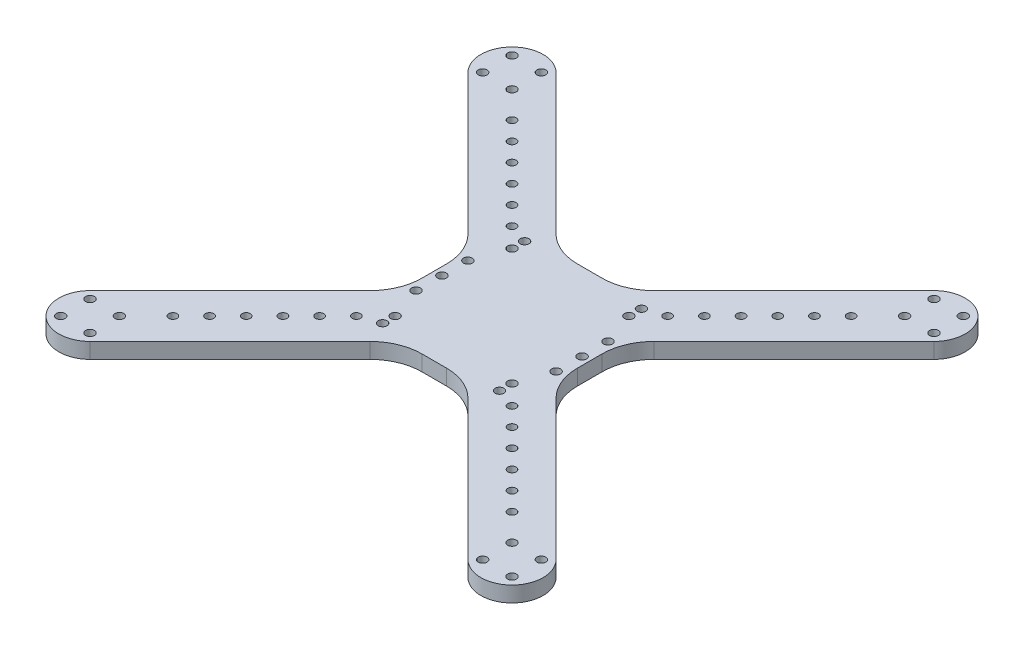
SolidWorks part; units mm, degrees
material "Carbon Fiber"
ref_plane "Front Plane" through (0, 0, 0) normal (0, 0, 1) x (1, 0, 0)
ref_plane "Top Plane" through (0, 0, 0) normal (0, 1, 0) x (1, 0, 0)
ref_plane "Right Plane" through (0, 0, 0) normal (1, 0, 0) x (0, 0, -1)
sketch "Sketch1" plane through (0, 0, 0) normal (0, 1, 0) x (1, 0, 0)
  line L0 (-81.3173, 81.3173) -> (81.3173, -81.3173) construction
  line L1 (-98.425, -98.425) -> (98.425, -98.425) construction
  line L2 (-98.425, -98.425) -> (-98.425, 98.425) construction
  line L3 (-98.425, 98.425) -> (98.425, 98.425) construction
  line L4 (98.425, -98.425) -> (98.425, 98.425) construction
  line L5 (-98.425, -98.425) -> (98.425, 98.425) construction
  line L6 (-98.425, 98.425) -> (98.425, -98.425) construction
  line L7 (-72.832, 89.8026) -> (-13.0294, 30)
  line L8 (-89.8026, 72.832) -> (-30, 13.0294)
  line L9 (0, 98.425) -> (0, -98.425) construction
  line L10 (81.3173, 81.3173) -> (-81.3173, -81.3173) construction
  line L11 (72.832, 89.8026) -> (13.0294, 30)
  line L12 (89.8026, 72.832) -> (30, 13.0294)
  line L13 (-30, -13.0294) -> (-89.8026, -72.832)
  line L14 (-13.0294, -30) -> (13.0294, -30)
  line L15 (-30, -13.0294) -> (-30, 13.0294)
  line L16 (-13.0294, 30) -> (13.0294, 30)
  line L17 (30, -13.0294) -> (30, 13.0294)
  line L18 (-30, -30) -> (30, 30) construction
  line L19 (-30, 30) -> (30, -30) construction
  line L20 (-13.0294, -30) -> (-72.832, -89.8026)
  line L21 (30, -13.0294) -> (89.8026, -72.832)
  line L22 (13.0294, -30) -> (72.832, -89.8026)
  arc A0 (-72.832, 89.8026) -> (-89.8026, 72.832) centre (-81.3173, 81.3173) ccw
  arc A1 (72.832, -89.8026) -> (89.8026, -72.832) centre (81.3173, -81.3173) ccw
  circle A2 centre (-81.3173, 81.3173) radius 8 construction
  circle A3 centre (81.3173, -81.3173) radius 8 construction
  circle A4 centre (-81.3173, -81.3173) radius 8 construction
  circle A5 centre (81.3173, 81.3173) radius 8 construction
  arc A6 (72.832, 89.8026) -> (89.8026, 72.832) centre (81.3173, 81.3173) cw
  arc A7 (-72.832, -89.8026) -> (-89.8026, -72.832) centre (-81.3173, -81.3173) cw
  point P0 (0, 0)
  point P8 (0, 0)
  point P23 (0, 0)
  point P29 (0, 0)
  point P42 (30, 0)
  dimension "D2" = 12
  dimension "D4" = 16
  dimension "D6" = 12
  dimension "D9" = 12
  dimension "D10" = 12
  dimension "D1" = 196.85
  dimension "D3" = 115
  dimension "D5" = 115
  dimension "D8" = 26.0589
  dimension "D11" = 30
  dimension "D12" = 30
extrude "Boss-Extrude1" add sketch "Sketch1" along normal blind 6
fillet "Fillet1" radius 20 8 edges at (-30, 3, -13.0294) (-30, 3, 13.0294) (-13.0294, 3, -30) (13.0294, 3, -30) (30, 3, 13.0294) (30, 3, -13.0294) (13.0294, 3, 30) (-13.0294, 3, 30)
ref_axis "Axis1" through (0, 6.3, 0) along (0, -1, 0)
ref_plane "Plane1" through (0, 0, 0) normal (-0.7071, 0, 0.7071) x (0, -1, 0)
sketch "Sketch2" plane through (0, 6, 0) normal (0, 1, 0) x (1, 0, 0)
  line L0 (0, 0) -> (-25, 0)
  line L1 (-25, 0) -> (-25, -25)
  line L2 (-25, -25) -> (0, -25)
  line L3 (0, -25) -> (0, 0)
  circle A1 centre (-22.525, -22.525) radius 1.7
  dimension "D4" = 3.4
  dimension "D1" = 25
  dimension "D2" = 22.525
  dimension "D3" = 22.525
extrude "Cut-Extrude1" cut sketch "Sketch2" against normal through all contours A1 region at (-22.525, 6, 22.525)
pattern_circular "CirPattern1" count 4 over 360 about axis through (0, 6.3, 0) along (0, -1, 0) of "Cut-Extrude1"
sketch "Sketch3" plane through (0, 6, 0) normal (0, 1, 0) x (1, 0, 0)
  line L0 (0, 0) -> (-89.8026, -89.8026) construction
  circle A0 centre (-30, -30) radius 1.6
  arc A1 (-89.8026, -72.832) -> (-72.832, -89.8026) centre (-81.3173, -81.3173) ccw construction
  dimension "D1" = 3.2
  dimension "D2" = 30
extrude "Cut-Extrude2" cut sketch "Sketch3" against normal through all
pattern_linear "LPattern1" count 6 spacing 10 along (-0.7071, 0, 0.7071) of "Cut-Extrude2"
pattern_circular "CirPattern2" count 4 over 360 about axis through (0, 6.3, 0) along (0, -1, 0) of "LPattern1"
sketch "Sketch4" plane through (0, 6, 0) normal (0, 1, 0) x (1, 0, 0)
  line L0 (-89.8026, -72.832) -> (-72.832, -89.8026) construction
  line L1 (-75.6604, -75.6604) -> (-86.9741, -86.9741) construction
  circle A0 centre (-81.3173, -81.3173) radius 8
  circle A1 centre (-86.9741, -86.9741) radius 1.7
  circle A2 centre (-86.9741, -75.6604) radius 1.7
  circle A3 centre (-75.6604, -75.6604) radius 1.7
  circle A4 centre (-75.6604, -86.9741) radius 1.7
  dimension "D1" = 16
  dimension "D2" = 3.4
extrude "Cut-Extrude3" cut sketch "Sketch4" against normal through all contours A0 A2 | A0 A2 | A0 A3 | A0 A3 | A0 A4 | A0 A4 | A0 A1 | A0 A1 region at (-76.1929, 6, 76.1929) region at (-75.1739, 6, 75.1739) region at (-75.1739, 6, 87.4606) region at (-76.1929, 6, 86.4416) region at (-86.4416, 6, 76.1929) region at (-87.4606, 6, 75.1739) region at (-87.4606, 6, 87.4606) region at (-86.4416, 6, 86.4416)
pattern_circular "CirPattern3" count 4 over 360 about axis through (0, 6.3, 0) along (0, -1, 0) of "Cut-Extrude3"
sketch "Sketch5" plane through (0, 6, 0) normal (0, 1, 0) x (1, 0, 0)
  line L0 (-22.525, -22.525) -> (-22.525, 27.375) construction
  line L1 (0, 0) -> (-22.525, 0) construction
  line L2 (-22.525, 0) -> (-22.525, -27.35) construction
  circle A0 centre (-22.525, 27.375) radius 1.7
  circle A1 centre (-22.525, -27.35) radius 1.7
  dimension "D2" = 3.4
  dimension "D5" = 3.4
  dimension "D1" = 49.9
  dimension "D3" = 27.375
  dimension "D4" = 27.35
extrude "Cut-Extrude4" cut sketch "Sketch5" against normal through all contours A0 | A1 region at (-22.525, 6, -27.375) region at (-22.525, 6, 27.35)
mirror "Mirror1" about plane through (0, 0, 0) normal (1, 0, 0) of "Cut-Extrude4"
sketch "Sketch6" plane through (0, 6, 0) normal (0, 1, 0) x (1, 0, 0)
  line L0 (-2.5668, 2.5668) -> (2.5668, -2.5668) construction
  line L1 (-89.8026, 72.832) -> (-72.832, 89.8026) construction
  circle A0 centre (-81.3173, 81.3173) radius 63.5
sketch "Sketch7" plane through (0, 6, 0) normal (0, 1, 0) x (1, 0, 0)
  line L0 (-30, 4.7452) -> (-30, -4.7452) construction
  line L1 (-27, 0) -> (0, 0) construction
  circle A0 centre (-27, 0) radius 1.7
  dimension "D1" = 3.4
  dimension "D2" = 3
extrude "Cut-Extrude5" cut sketch "Sketch7" against normal through all
pattern_linear "LPattern2" count 2 spacing 10 along (0, 0, 1) count 2 spacing 10 along (0, 0, -1) of "Cut-Extrude5"
mirror "Mirror2" about plane through (0, 0, 0) normal (1, 0, 0) of "LPattern2"
